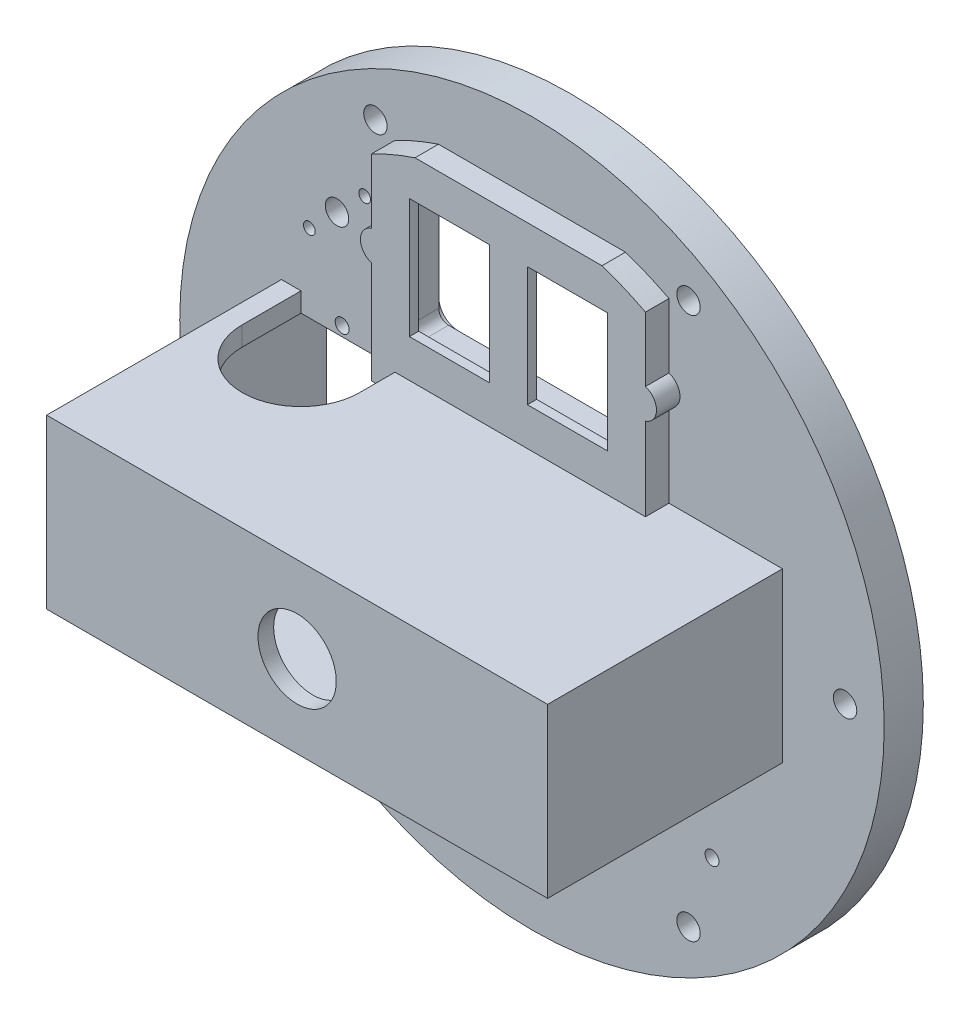
SolidWorks part; units mm, degrees
ref_plane "Front Plane" through (0, 0, 0) normal (0, 0, 1) x (1, 0, 0)
ref_plane "Top Plane" through (0, 0, 0) normal (0, 1, 0) x (1, 0, 0)
ref_plane "Right Plane" through (0, 0, 0) normal (1, 0, 0) x (0, 0, -1)
sketch "Sketch1" plane through (0, 0, 0) normal (0, 0, 1) x (1, 0, 0)
  circle A0 centre (0, 0) radius 57.15
  dimension "D1" = 114.3
extrude "Boss-Extrude1" add sketch "Sketch1" along normal blind 6.35
sketch "Sketch2" plane through (0, 0, 6.35) normal (0, 0, 1) x (1, 0, 0)
  line L0 (22.225, 13.9303) -> (22.225, 45.6803)
  line L1 (-22.225, 45.6803) -> (22.225, 45.6803)
  line L2 (-22.225, 45.6803) -> (-22.225, 13.9303)
  line L3 (-22.225, 13.9303) -> (22.225, 13.9303)
  line L9 (0, 13.9303) -> (0, 45.6803) construction
  line L10 (0, 0) -> (0, 57.15) construction
  circle A1 centre (0, 0) radius 57.15 construction
  circle A2 centre (0, 0) radius 50.8 construction
  dimension "D3" = 6.35
  dimension "D1" = 44.45
  dimension "D2" = 31.75
extrude "Boss-Extrude2" add sketch "Sketch2" along normal blind 3.81 contours L1 L0 L3 L2
sketch "Sketch3" plane through (0, 0, 10.16) normal (0, 0, 1) x (1, 0, 0)
  line L0 (0, 45.6803) -> (0, 13.9303) construction
  line L1 (-16.075, 39.5053) -> (-3.075, 39.5053)
  line L2 (-16.075, 39.5053) -> (-16.075, 20.1053)
  line L3 (-16.075, 20.1053) -> (-3.075, 20.1053)
  line L4 (-3.075, 39.5053) -> (-3.075, 20.1053)
  line L5 (3.075, 39.5053) -> (16.075, 39.5053)
  line L6 (3.075, 39.5053) -> (3.075, 20.1053)
  line L7 (3.075, 20.1053) -> (16.075, 20.1053)
  line L8 (16.075, 39.5053) -> (16.075, 20.1053)
  line L9 (-22.225, 45.6803) -> (22.225, 45.6803) construction
  line L10 (-22.225, 13.9303) -> (22.225, 13.9303) construction
  line L11 (-22.225, 29.8053) -> (-16.075, 29.8053) construction
  line L12 (-22.225, 45.6803) -> (-22.225, 13.9303) construction
  line L13 (16.075, 29.8053) -> (22.225, 29.8053) construction
  line L14 (22.225, 13.9303) -> (22.225, 45.6803) construction
  line L15 (-3.075, 29.8053) -> (3.075, 29.8053) construction
  dimension "D1" = 19.4
  dimension "D2" = 13
  dimension "D3" = 13
  dimension "D4" = 19.4
extrude "Cut-Extrude1" cut sketch "Sketch3" against normal through all
sketch "Sketch4" plane through (0, 0, 0) normal (0, 0, -1) x (-1, 0, 0)
  line L0 (16.075, 20.1053) -> (3.075, 20.1053) construction
  line L1 (-19.885, 43.3153) -> (19.885, 43.3153)
  line L2 (-19.885, 43.3153) -> (-19.885, 16.2953)
  line L3 (-19.885, 16.2953) -> (19.885, 16.2953)
  line L4 (19.885, 43.3153) -> (19.885, 16.2953)
  line L5 (3.075, 39.5053) -> (16.075, 39.5053) construction
  line L6 (16.075, 39.5053) -> (16.075, 20.1053) construction
  line L7 (-16.075, 20.1053) -> (-16.075, 39.5053) construction
  dimension "D1" = 3.81
  dimension "D2" = 3.81
  dimension "D3" = 3.81
  dimension "D4" = 3.81
extrude "Cut-Extrude2" cut sketch "Sketch4" against normal offset from surface (8.66 mm away) 1.5 up to face at (-9.575, 29.8053, 10.16)
fillet "Fillet1" radius 1.5875 4 edges at (19.885, 16.2953, 4.33) (-19.885, 16.2953, 4.33) (-19.885, 43.3153, 4.33) (19.885, 43.3153, 4.33)
sketch "Sketch8" plane through (0, 0, 0) normal (0, 0, -1) x (-1, 0, 0)
  line L0 (-19.885, 41.7278) -> (-19.885, 17.8828) construction
  line L1 (-18.2975, 16.2953) -> (18.2975, 16.2953) construction
  line L2 (19.885, 17.8828) -> (19.885, 41.7278) construction
  line L3 (18.2975, 43.3153) -> (-18.2975, 43.3153) construction
  line L4 (-19.885, 41.7278) -> (-19.885, 17.8828)
  line L5 (-18.2975, 16.2953) -> (18.2975, 16.2953)
  line L6 (19.885, 17.8828) -> (19.885, 41.7278)
  line L7 (18.2975, 43.3153) -> (-18.2975, 43.3153)
  line L8 (18.2975, 44.9028) -> (-18.2975, 44.9028)
  line L9 (-21.4725, 41.7278) -> (-21.4725, 17.8828) construction
  line L10 (-18.2975, 14.7078) -> (18.2975, 14.7078)
  line L11 (21.4725, 17.8828) -> (21.4725, 41.7278) construction
  line L12 (-21.4725, 32.9803) -> (-21.4725, 41.7278)
  line L13 (-21.4725, 26.6303) -> (-21.4725, 17.8828)
  line L14 (21.4725, 17.8828) -> (21.4725, 26.6303)
  line L15 (21.4725, 32.9803) -> (21.4725, 41.7278)
  arc A0 (-18.2975, 43.3153) -> (-19.885, 41.7278) centre (-18.2975, 41.7278) ccw construction
  circle A1 centre (0, 0) radius 57.15
  circle A2 centre (0, 0) radius 57.15
  arc A3 (-19.885, 17.8828) -> (-18.2975, 16.2953) centre (-18.2975, 17.8828) ccw construction
  arc A4 (18.2975, 16.2953) -> (19.885, 17.8828) centre (18.2975, 17.8828) ccw construction
  arc A5 (19.885, 41.7278) -> (18.2975, 43.3153) centre (18.2975, 41.7278) ccw construction
  arc A6 (-18.2975, 43.3153) -> (-19.885, 41.7278) centre (-18.2975, 41.7278) ccw
  arc A7 (-19.885, 17.8828) -> (-18.2975, 16.2953) centre (-18.2975, 17.8828) ccw
  arc A8 (18.2975, 16.2953) -> (19.885, 17.8828) centre (18.2975, 17.8828) ccw
  arc A9 (19.885, 41.7278) -> (18.2975, 43.3153) centre (18.2975, 41.7278) ccw
  arc A10 (-18.2975, 44.9028) -> (-21.4725, 41.7278) centre (-18.2975, 41.7278) ccw
  arc A11 (-21.4725, 17.8828) -> (-18.2975, 14.7078) centre (-18.2975, 17.8828) ccw
  arc A12 (18.2975, 14.7078) -> (21.4725, 17.8828) centre (18.2975, 17.8828) ccw
  arc A13 (21.4725, 41.7278) -> (18.2975, 44.9028) centre (18.2975, 41.7278) ccw
  arc A14 (21.4725, 26.6303) -> (21.4725, 32.9803) centre (21.4725, 29.8053) ccw
  arc A15 (-21.4725, 32.9803) -> (-21.4725, 26.6303) centre (-21.4725, 29.8053) ccw
  dimension "D3" = 6.35
  dimension "D4" = 6.35
  dimension "D1" = 0
  dimension "D2" = 1.5875
extrude "Cut-Extrude3" cut sketch "Sketch8" against normal blind 1.5875 contours L12 A10 L8 A13 L15 A14 L14 A12 L10 A11 L13 A15
hole_wizard "CBORE for #6 Pan Head Machine Screw1" positions "Sketch9" profile "Sketch10" counterbore size "#6" standard "ANSI Inch" end condition through all
sketch "Sketch9" plane through (0, 0, 0) normal (0, 0, -1) x (-1, 0, 0)
  line L0 (0, 0) -> (-50.8, 0) construction
  line L2 (-50.8, 0) -> (-57.15, 0)
  circle A1 centre (0, 0) radius 57.15 construction
  point P0 (-50.8, 0)
  dimension "D1" = 50.8
sketch "Sketch10" plane through (50.8, 0, 0) normal (1, 0, 0) x (0, 1, 0)
  line L0 (0, 0) -> (0, 10.16)
  line L1 (0, 10.16) -> (1.8986, 10.16)
  line L3 (1.8986, 10.16) -> (1.8987, 2.4638)
  line L4 (1.8987, 2.4638) -> (3.7706, 2.4638)
  line L5 (3.7706, 2.4638) -> (3.7706, 0)
  line L7 (3.7706, 0) -> (0, 0)
  line L11 (0, -6.35) -> (0, 107.95) construction
  dimension "Thru Hole Dia." = 3.7973
  dimension "Thru Hole Depth" = 10.16
  dimension "C'Bore Dia." = 7.5413
  dimension "C'Bore Depth" = 2.4638
pattern_circular "CirPattern1" count 6 over 360 about axis through (0, 0, 6.35) along (0, 0, -1) of "CBORE for #6 Pan Head Machine Screw1" reverse direction yes
sketch "Sketch11" plane through (0, 0, 0) normal (0, 0, -1) x (-1, 0, 0)
  line L0 (-38.1, 0) -> (0, 0) construction
  line L1 (-38.1, 10.795) -> (38.1, 10.795)
  line L2 (-38.1, 10.795) -> (-38.1, -10.795)
  line L3 (-38.1, -10.795) -> (38.1, -10.795)
  line L4 (38.1, 10.795) -> (38.1, -10.795)
  line L5 (0, 0) -> (38.1, 0) construction
  line L6 (0, 10.795) -> (0, 0) construction
  dimension "D1" = 76.2
  dimension "D2" = 21.59
extrude "Cut-Extrude4" cut sketch "Sketch11" against normal through all
sketch "Sketch12" plane through (0, 0, 0) normal (0, 0, -1) x (-1, 0, 0)
  line L0 (38.1, 10.795) -> (-38.1, 10.795) construction
  line L1 (-39.6875, 12.3825) -> (-33.9725, 12.3825)
  line L2 (-39.6875, 12.3825) -> (-39.6875, -12.3825)
  line L3 (-39.6875, -12.3825) -> (-3.175, -12.3825)
  line L4 (39.6875, 12.3825) -> (39.6875, -12.3825)
  line L5 (38.1, -10.795) -> (-38.1, -10.795) construction
  line L6 (-38.1, 10.795) -> (-38.1, -10.795) construction
  line L7 (38.1, -10.795) -> (38.1, 10.795) construction
  line L8 (0, 0) -> (0, -12.3825) construction
  line L9 (-27.6225, 12.3825) -> (27.6225, 12.3825)
  line L10 (3.175, -12.3825) -> (39.6875, -12.3825)
  line L11 (33.9725, 12.3825) -> (39.6875, 12.3825)
  line L12 (0, -12.3825) -> (3.175, -12.3825) construction
  arc A0 (-27.6225, 12.3825) -> (-33.9725, 12.3825) centre (-30.7975, 12.3825) ccw
  arc A1 (-3.175, -12.3825) -> (3.175, -12.3825) centre (0, -12.3825) ccw
  arc A3 (33.9725, 12.3825) -> (27.6225, 12.3825) centre (30.7975, 12.3825) ccw
  dimension "D5" = 6.35
  dimension "D1" = 1.5875
  dimension "D2" = 1.5875
  dimension "D3" = 1.5875
  dimension "D4" = 1.5875
  dimension "D6" = 8.89
  dimension "D7" = 8.89
extrude "Cut-Extrude5" cut sketch "Sketch12" against normal up to surface (1.5875 mm away) up to face at (0, 29.8053, 1.5875)
sketch "Sketch15" plane through (0, 0, 6.35) normal (0, 0, 1) x (1, 0, 0)
  line L1 (-40.64, 13.9303) -> (40.64, 13.9303)
  line L2 (-40.64, 13.9303) -> (-40.64, -13.335)
  line L3 (-40.64, -13.335) -> (40.64, -13.335)
  line L4 (40.64, 13.9303) -> (40.64, -13.335)
  line L5 (-22.225, 13.9303) -> (22.225, 13.9303) construction
  line L6 (-38.1, -10.795) -> (38.1, -10.795) construction
  line L7 (38.1, -10.795) -> (38.1, 10.795) construction
  line L8 (-38.1, 10.795) -> (-38.1, -10.795) construction
  line L10 (-38.1, 10.795) -> (38.1, 10.795)
  line L11 (-38.1, 10.795) -> (-38.1, -10.795)
  line L12 (-38.1, -10.795) -> (38.1, -10.795)
  line L13 (38.1, 10.795) -> (38.1, -10.795)
  dimension "D1" = 2.54
  dimension "D2" = 2.54
  dimension "D3" = 2.54
extrude "Boss-Extrude3" add sketch "Sketch15" along normal blind 38.1
sketch "Sketch16" plane through (0, -13.335, 0) normal (0, -1, 0) x (1, 0, 0)
  line L0 (-40.64, 6.35) -> (40.64, 6.35) construction
  line L1 (30.0233, 6.35) -> (4.6233, 6.35)
  line L2 (30.0233, 6.35) -> (30.0233, 31.75)
  line L3 (30.0233, 31.75) -> (4.6233, 31.75)
  line L4 (4.6233, 6.35) -> (4.6233, 31.75)
  dimension "D1" = 25.4
  dimension "D2" = 25.4
extrude "Cut-Extrude6" cut sketch "Sketch16" against normal up to next
fillet "Fillet2" radius 12.7 2 edges at (4.6233, -12.065, 31.75) (30.0233, -12.065, 31.75)
sketch "Sketch17" plane through (0, 0, 44.45) normal (0, 0, 1) x (1, 0, 0)
  line L1 (-40.64, 13.9303) -> (40.64, 13.9303)
  line L2 (-40.64, 13.9303) -> (-40.64, -13.335)
  line L3 (-40.64, -13.335) -> (40.64, -13.335)
  line L4 (40.64, 13.9303) -> (40.64, -13.335)
extrude "Boss-Extrude4" add sketch "Sketch17" against normal blind 2.54
hole_wizard "#4-40 Tapped Hole1" positions "Sketch13" profile "Sketch14" tap size "#4-40" standard "ANSI Inch"
sketch "Sketch13" plane through (0, 0, 1.5875) normal (0, 0, -1) x (-1, 0, 0)
  point P0 (0, -12.3825)
  point P3 (30.7975, 12.3825)
  point P6 (21.4725, 29.8053)
  point P9 (-21.4725, 29.8053)
  point P12 (-30.7975, 12.3825)
sketch "Sketch14" plane through (0, -12.3825, 1.5875) normal (1, 0, 0) x (0, 1, 0)
  line L0 (0, 0) -> (0, 8.2738)
  line L1 (0, 8.2738) -> (1.1303, 7.5946)
  line L2 (1.1303, 7.5946) -> (1.1303, 0)
  line L5 (1.1303, 0) -> (0, 0)
  line L10 (0, 8.2738) -> (-1.1303, 7.5946) construction
  line L11 (0, -6.35) -> (0, 107.95) construction
  dimension "Tap Drill Dia." = 2.2606
  dimension "Tap Drill Depth" = 7.5946
  dimension "Drill Angle" = 118
sketch "Sketch21" plane through (0, 0, 10.16) normal (0, 0, 1) x (1, 0, 0)
  line L1 (-21.4725, 32.3453) -> (-21.4725, 27.2653)
  line L2 (21.4725, 32.3453) -> (21.4725, 27.2653)
  arc A0 (-21.4725, 32.3453) -> (-21.4725, 27.2653) centre (-21.4725, 29.8053) ccw
  arc A1 (21.4725, 27.2653) -> (21.4725, 32.3453) centre (21.4725, 29.8053) ccw
  arc A2 (22.225, 28.9619) -> (22.225, 30.6487) centre (21.4725, 29.8053) ccw construction
  dimension "D1" = 5.08
  dimension "D2" = 5.08
extrude "Boss-Extrude5" add sketch "Sketch21" against normal up to surface (3.81 mm away) up to face at (3.8496, 9.1403, 6.35)
sketch "Sketch18" plane through (0, 0, 0) normal (0, 0, -1) x (-1, 0, 0)
  line L0 (31.6325, 27.9003) -> (21.4725, 27.9003) construction
  line L1 (21.4725, 29.8053) -> (21.4725, 27.9003) construction
  circle A0 centre (31.6325, 27.9003) radius 1.905
  arc A1 (22.225, 27.3793) -> (22.225, 32.2313) centre (21.4725, 29.8053) ccw construction
  dimension "D1" = 3.81
  dimension "D2" = 10.16
  dimension "D3" = 1.905
extrude "Cut-Extrude7" cut sketch "Sketch18" against normal through all
sketch "Sketch19" plane through (0, 0, 6.35) normal (0, 0, 1) x (1, 0, 0)
  line L0 (-31.6325, 27.9003) -> (-27.1424, 32.3904) construction
  line L1 (-31.6325, 27.9003) -> (-36.1226, 23.4102) construction
  line L2 (-31.6325, 27.9003) -> (-16.3925, 27.9003) construction
  circle A0 centre (-36.1226, 23.4102) radius 0.9525
  circle A1 centre (-27.1424, 32.3904) radius 0.9525
  dimension "D2" = 1.905
  dimension "D3" = 1.905
  dimension "D1" = 12.7
  dimension "D4" = 15.24
  dimension "D5" = 45
extrude "Cut-Extrude8" cut sketch "Sketch19" against normal offset from surface (4.7625 mm away) 1.5875 up to face at (-33.5375, 27.9003, 0)
sketch "Sketch20" plane through (0, 13.9303, 0) normal (0, 1, 0) x (1, 0, 0)
  line L1 (-40.64, -44.45) -> (-40.64, -6.35) construction
  line L2 (-37.465, -15.9004) -> (-37.465, -6.35)
  line L3 (-22.225, -6.35) -> (-40.64, -6.35) construction
  line L4 (-37.465, -6.35) -> (-18.415, -6.35) construction
  line L5 (-22.225, -6.35) -> (22.225, -6.35) construction
  line L6 (-18.415, -6.35) -> (-18.415, -15.9004) construction
  line L7 (-37.465, -6.35) -> (-22.225, -6.35)
  line L8 (-22.225, -6.35) -> (-22.225, -10.16)
  line L9 (-22.225, -10.16) -> (-18.415, -10.16)
  line L10 (-22.225, -10.16) -> (22.225, -10.16) construction
  line L11 (-18.415, -10.16) -> (-18.415, -15.9004)
  arc A0 (-37.465, -15.9004) -> (-18.415, -15.9004) centre (-27.94, -15.9004) ccw
  dimension "D1" = 19.05
  dimension "D2" = 12.7
  dimension "D3" = 9.5504
extrude "Cut-Extrude9" cut sketch "Sketch20" against normal up to next
sketch "Sketch23" plane through (0, 0, 1.5875) normal (0, 0, -1) x (-1, 0, 0)
  circle A0 centre (-21.4725, 29.8053) radius 1.1303
  circle A1 centre (-21.4725, 29.8053) radius 1.1303 construction
  circle A2 centre (21.4725, 29.8053) radius 1.1303
  circle A3 centre (21.4725, 29.8053) radius 1.1303 construction
extrude "Cut-Extrude11" cut sketch "Sketch23" against normal up to vertex (8.2738 mm away) up to point (21.4725, 29.8053, 9.8613)
hole_wizard "#4-40 Tapped Hole2" positions "Sketch24" profile "Sketch25" tap size "#4-40" standard "ANSI Inch"
sketch "Sketch24" plane through (0, 0, 6.35) normal (0, 0, 1) x (1, 0, 0)
  line L0 (-34.29, -32.385) -> (-34.29, -19.685)
  line L2 (-40.64, -13.335) -> (40.64, -13.335) construction
  point P0 (-34.29, -19.685)
  point P2 (-34.29, -32.385)
  dimension "D1" = 12.7
  dimension "D2" = 6.35
  dimension "D3" = 6.35
sketch "Sketch25" plane through (-34.29, -19.685, 6.35) normal (1, 0, 0) x (0, -1, 0)
  line L0 (0, 0) -> (0, 5.4544)
  line L1 (0, 5.4544) -> (1.1303, 4.7752)
  line L2 (1.1303, 4.7752) -> (1.1303, 0)
  line L5 (1.1303, 0) -> (0, 0)
  line L10 (0, 5.4544) -> (-1.1303, 4.7752) construction
  line L11 (0, -6.35) -> (0, 107.95) construction
  dimension "Tap Drill Dia." = 2.2606
  dimension "Tap Drill Depth" = 4.7752
  dimension "Drill Angle" = 118
cosmetic thread "Hole Thread1" parameters "D1"=4.7752, "D2"=2.8448
cosmetic thread "Hole Thread2" parameters "D1"=4.7752, "D2"=2.8448
pattern_linear "LPattern1" count 6 spacing 12.7 along (1, 0, 0) of "#4-40 Tapped Hole2"
sketch "Sketch26" plane through (0, 0, 0) normal (0, 0, -1) x (-1, 0, 0)
  circle A0 centre (0, 0) radius 6.35
  dimension "D1" = 12.7
extrude "Cut-Extrude12" cut sketch "Sketch26" against normal through all
sketch "Sketch27" plane through (0, 0, 6.35) normal (0, 0, 1) x (1, 0, 0)
  circle A0 centre (0, 0) radius 48.133
  circle A1 centre (0, 0) radius 63.5
  dimension "D1" = 96.266
  dimension "D2" = 127
extrude "Cut-Extrude14" cut sketch "Sketch27" along normal through all
